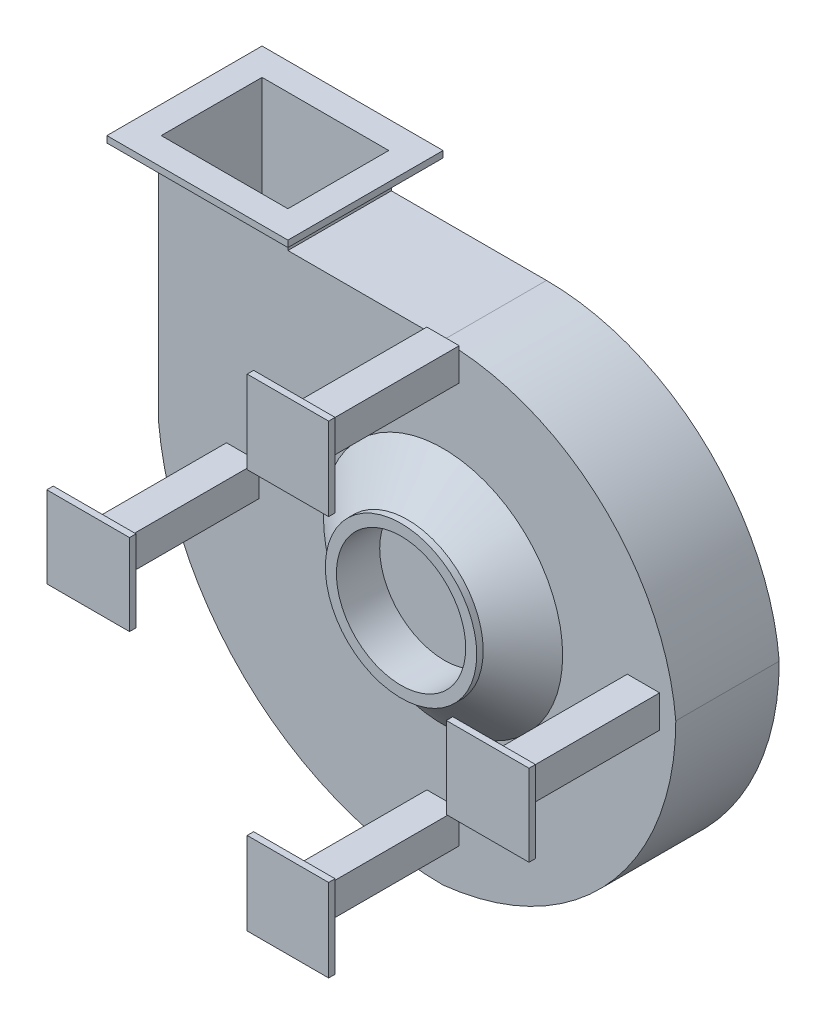
SolidWorks part; units mm, degrees
ref_plane "Front Plane" through (0, 0, 0) normal (0, 0, 1) x (1, 0, 0)
ref_plane "Top Plane" through (0, 0, 0) normal (0, 1, 0) x (1, 0, 0)
ref_plane "Right Plane" through (0, 0, 0) normal (1, 0, 0) x (0, 0, -1)
sketch "Sketch1" plane through (0, 0, 0) normal (0, 0, 1) x (1, 0, 0)
  line L0 (-181.4248, -189.9736) -> (618.5752, -189.9736) construction
  line L1 (258.5752, 140.0264) -> (258.5752, -589.9736) construction
  line L2 (-181.4248, -189.9736) -> (-181.4248, 184.0264)
  line L3 (-181.4248, 184.0264) -> (18.5752, 184.0264)
  line L4 (18.5752, 184.0264) -> (18.5752, 140.0264)
  line L5 (18.5752, 140.0264) -> (258.5752, 140.0264)
  arc A0 (258.5752, 140.0264) -> (618.5752, -189.9736) centre (258.5752, -221.3373) cw
  arc A1 (618.5752, -189.9736) -> (258.5752, -589.9736) centre (216.353, -189.9736) cw
  arc A2 (258.5752, -589.9736) -> (-181.4248, -189.9736) centre (258.5752, -147.9736) cw
  dimension "D1" = 800
  dimension "D2" = 730
  dimension "D3" = 330
  dimension "D4" = 360
  dimension "D5" = 44
  dimension "D6" = 200
extrude "Boss-Extrude1" add sketch "Sketch1" along normal blind 160
shell "Shell4" thickness 2 removed face at (-81.4248, 184.0264, 80)
sketch "Sketch5" plane through (0, 0, 160) normal (0, 0, 1) x (1, 0, 0)
  line L1 (-181.4248, -189.9736) -> (618.5752, -189.9736) construction
  line L2 (258.5752, 140.0264) -> (258.5752, -589.9736) construction
  circle A0 centre (258.5752, -189.9736) radius 90
  dimension "D1" = 180
extrude "Cut-Extrude1" cut sketch "Sketch5" against normal blind 118
sketch "Sketch6" plane through (0, 0, 160) normal (0, 0, 1) x (1, 0, 0)
  circle A0 centre (258.5752, -189.9736) radius 185
extrude "Boss-Extrude2" add sketch "Sketch6" along normal blind 55 draft 51
sketch "Sketch7" plane through (0, 0, 215) normal (0, 0, 1) x (1, 0, 0)
  circle A1 centre (258.5752, -189.9736) radius 117.0807
  circle A2 centre (258.5752, -189.9736) radius 117.0807
  dimension "D1" = 0
extrude "Boss-Extrude3" add sketch "Sketch7" along normal blind 10
sketch "Sketch9" plane through (0, 0, 225) normal (0, 0, 1) x (1, 0, 0)
  circle A0 centre (258.5752, -189.9736) radius 100
extrude "Cut-Extrude2" cut sketch "Sketch9" against normal blind 118
sketch "Sketch11" plane through (0, 0, 0) normal (0, 0, -1) x (-1, 0, 0)
  line L1 (181.4248, -189.9736) -> (-618.5752, -189.9736) construction
  circle A0 centre (-258.5752, -189.9736) radius 10
extrude "Cut-Extrude3" cut sketch "Sketch11" against normal blind 118
sketch "Sketch12" plane through (0, 184.0264, 0) normal (0, 1, 0) x (1, 0, 0)
  line L2 (-221.4248, 40) -> (58.5752, 40)
  line L3 (-221.4248, 40) -> (-221.4248, -200)
  line L4 (-221.4248, -200) -> (58.5752, -200)
  line L5 (58.5752, 40) -> (58.5752, -200)
  line L6 (-221.4248, 40) -> (58.5752, -200) construction
  line L7 (-221.4248, -200) -> (58.5752, 40) construction
  line L8 (-179.4248, -158) -> (16.5752, -158)
  line L9 (-179.4248, -158) -> (-179.4248, -2)
  line L10 (-179.4248, -2) -> (16.5752, -2)
  line L11 (16.5752, -158) -> (16.5752, -2)
  line L12 (-179.4248, -158) -> (16.5752, -2) construction
  line L13 (-179.4248, -2) -> (16.5752, -158) construction
  point P4 (-81.4248, -80)
  point P9 (-81.4248, -80)
  dimension "D1" = 280
  dimension "D2" = 240
extrude "Boss-Extrude4" add sketch "Sketch12" along normal blind 10
sketch "Sketch13" plane through (0, 0, 160) normal (0, 0, 1) x (1, 0, 0)
  line L0 (-181.4248, -189.9736) -> (618.5752, -189.9736) construction
  line L1 (-76.4248, -164.9736) -> (-26.4248, -164.9736)
  line L2 (-76.4248, -164.9736) -> (-76.4248, -214.9736)
  line L3 (-76.4248, -214.9736) -> (-26.4248, -214.9736)
  line L4 (-26.4248, -164.9736) -> (-26.4248, -214.9736)
  line L5 (-76.4248, -164.9736) -> (-26.4248, -214.9736) construction
  line L6 (-76.4248, -214.9736) -> (-26.4248, -164.9736) construction
  line L7 (258.5752, 140.0264) -> (258.5752, -589.9736) construction
  line L8 (233.5752, 145.0264) -> (233.5752, 95.0264)
  line L9 (283.5752, 145.0264) -> (233.5752, 145.0264)
  line L10 (283.5752, 95.0264) -> (233.5752, 95.0264)
  line L11 (283.5752, 145.0264) -> (283.5752, 95.0264)
  line L12 (593.5752, -164.9736) -> (543.5752, -164.9736)
  line L13 (593.5752, -214.9736) -> (593.5752, -164.9736)
  line L14 (543.5752, -214.9736) -> (543.5752, -164.9736)
  line L15 (593.5752, -214.9736) -> (543.5752, -214.9736)
  line L16 (283.5752, -524.9736) -> (283.5752, -474.9736)
  line L17 (233.5752, -524.9736) -> (283.5752, -524.9736)
  line L18 (233.5752, -474.9736) -> (283.5752, -474.9736)
  line L19 (233.5752, -524.9736) -> (233.5752, -474.9736)
  point P0 (-51.4248, -189.9736)
  point P24 (258.5752, -189.9736)
  dimension "D1" = 310
  dimension "D2" = 50
  dimension "D3" = 50
  dimension "D4" = 4
extrude "Extrude-Thin1" add sketch "Sketch13" along normal blind 230 thin thin type one direction reverse wall 2
sketch "Sketch15" plane through (0, 0, 160) normal (0, 0, 1) x (1, 0, 0)
  line L8 (258.5752, 140.0264) -> (258.5752, -589.9736) construction
  line L9 (195.5752, -434.9736) -> (321.5752, -434.9736)
  line L10 (195.5752, -434.9736) -> (195.5752, -562.9736)
  line L11 (195.5752, -562.9736) -> (321.5752, -562.9736)
  line L12 (321.5752, -434.9736) -> (321.5752, -562.9736)
  line L13 (195.5752, -434.9736) -> (321.5752, -562.9736) construction
  line L14 (195.5752, -562.9736) -> (321.5752, -434.9736) construction
  line L15 (283.5752, -474.9736) -> (233.5752, -474.9736) construction
  line L16 (13.5752, -126.9736) -> (-114.4248, -126.9736)
  line L17 (13.5752, -126.9736) -> (13.5752, -252.9736)
  line L18 (13.5752, -252.9736) -> (-114.4248, -252.9736)
  line L19 (-114.4248, -126.9736) -> (-114.4248, -252.9736)
  line L20 (321.5752, 55.0264) -> (321.5752, 183.0264)
  line L21 (321.5752, 55.0264) -> (195.5752, 55.0264)
  line L22 (195.5752, 55.0264) -> (195.5752, 183.0264)
  line L23 (321.5752, 183.0264) -> (195.5752, 183.0264)
  line L24 (503.5752, -252.9736) -> (631.5752, -252.9736)
  line L25 (503.5752, -252.9736) -> (503.5752, -126.9736)
  line L26 (503.5752, -126.9736) -> (631.5752, -126.9736)
  line L27 (631.5752, -252.9736) -> (631.5752, -126.9736)
  point P2 (258.5752, -498.9736)
  point P28 (258.5752, -189.9736)
  dimension "D2" = 40
  dimension "D4" = 4
extrude "Boss-Extrude6" add sketch "Sketch15" along normal blind 10 from offset 230
